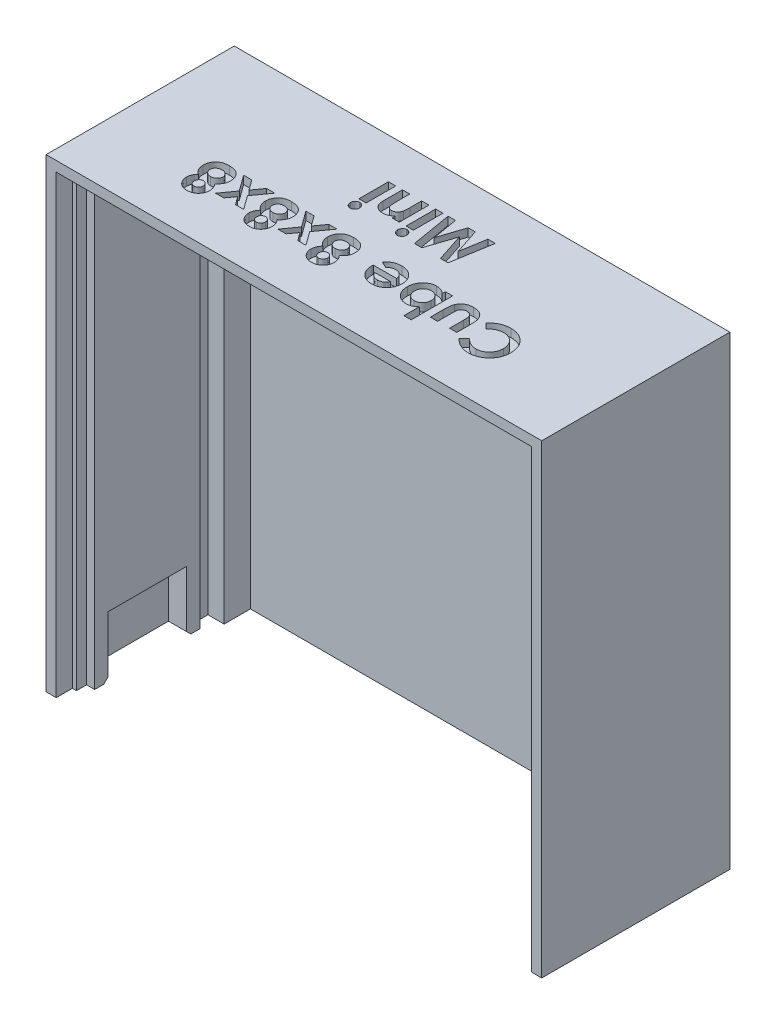
SolidWorks part; units mm, degrees
ref_plane "Plan de face" through (0, 0, 0) normal (0, 0, 1) x (1, 0, 0)
ref_plane "Plan de dessus" through (0, 0, 0) normal (0, 1, 0) x (1, 0, 0)
ref_plane "Plan de droite" through (0, 0, 0) normal (1, 0, 0) x (0, 0, -1)
sketch "Esquisse1" plane through (0, 0, 0) normal (0, 0, 1) x (1, 0, 0)
  line L1 (24.5, -23) -> (-24.5, -23)
  line L2 (24.5, -23) -> (24.5, 23)
  line L3 (24.5, 23) -> (-24.5, 23)
  line L4 (-24.5, -23) -> (-24.5, 23)
  line L5 (24.5, -23) -> (-24.5, 23) construction
  line L6 (24.5, 23) -> (-24.5, -23) construction
  point P0 (0, 0)
  dimension "D1" = 46
  dimension "D2" = 49
extrude "Boss.-Extru.1" add sketch "Esquisse1" along normal blind 1.4
sketch "Esquisse2" plane through (0, 0, 1.4) normal (0, 0, 1) x (1, 0, 0)
  line L0 (-24.5, -23) -> (-24.5, 23)
  line L1 (-24.5, 23) -> (24.5, 23)
  line L2 (24.5, 23) -> (24.5, -23)
  line L3 (24.5, -23) -> (21.5, -23)
  line L4 (-24.5, -23) -> (24.5, -23) construction
  line L5 (21.5, -23) -> (21.5, 20)
  line L6 (21.5, 20) -> (-21.5, 20)
  line L7 (-21.5, 20) -> (-21.5, -23)
  line L8 (-21.5, -23) -> (-24.5, -23)
  dimension "D1" = 3
  dimension "D2" = 3
  dimension "D3" = 3
extrude "Boss.-Extru.2" add sketch "Esquisse2" along normal blind 17.2
sketch3d "Esquisse3D1"
  line L0 (-21.5, 20, 18.6) -> (-21.5, 20, 1.4) construction
  line L1 (-21.5, 20, 4) -> (-21.5, 20, 5.6)
  line L2 (-21.5, 20, 4) -> (-21.5, -23, 4)
  line L3 (-21.5, -23, 4) -> (-21.5, -23, 5.6)
  line L4 (-21.5, 20, 5.6) -> (-21.5, -23, 5.6)
  line L5 (-21.5, -23, 18.6) -> (-21.5, -23, 1.4) construction
  line L7 (-21.5, 20, 16) -> (-21.5, 20, 17.6)
  line L8 (-21.5, 20, 16) -> (-21.5, -23, 16)
  line L9 (-21.5, -23, 16) -> (-21.5, -23, 17.6)
  line L10 (-21.5, 20, 17.6) -> (-21.5, -23, 17.6)
  point P8 (-21.5, -23, 1.4)
  dimension "D1" = 1.6
  dimension "D2" = 2.6
  dimension "D3" = 1.6
  dimension "D4" = 10.4
extrude "Enlèv. mat.-Extru.1" cut sketch "Esquisse3D1" along direction (-1, 0, 0) on the side against the normal blind 1.6 contours L8 L7 L10 L9 | L2 L1 L4 L3
sketch "Esquisse6" plane through (21.5, 0, 0) normal (-1, 0, 0) x (0, 0, 1)
  line L0 (18.6, 20) -> (1.4, 20) construction
  line L1 (4, 20) -> (5.6, 20)
  line L2 (4, 20) -> (4, -23)
  line L3 (4, -23) -> (5.6, -23)
  line L4 (5.6, 20) -> (5.6, -23)
  line L5 (18.6, -23) -> (1.4, -23) construction
  line L6 (1.4, 20) -> (1.4, -23) construction
  line L7 (16, -23) -> (17.6, -23)
  line L8 (16, -23) -> (16, 20)
  line L9 (16, 20) -> (17.6, 20)
  line L10 (17.6, -23) -> (17.6, 20)
  dimension "D1" = 1.6
  dimension "D2" = 1.6
  dimension "D3" = 2.6
  dimension "D4" = 10.4
extrude "Enlèv. mat.-Extru.2" cut sketch "Esquisse6" against normal blind 1.6
sketch "Esquisse7" plane through (0, 20, 0) normal (0, -1, 0) x (1, 0, 0)
  line L1 (-23.1, 17.6) -> (23.1, 17.6)
  line L2 (-23.1, 17.6) -> (-23.1, 16)
  line L3 (-23.1, 16) -> (23.1, 16)
  line L4 (23.1, 17.6) -> (23.1, 16)
  line L5 (-23.1, 4) -> (23.1, 4)
  line L6 (-23.1, 4) -> (-23.1, 5.6)
  line L7 (-23.1, 5.6) -> (23.1, 5.6)
  line L8 (23.1, 4) -> (23.1, 5.6)
extrude "Enlèv. mat.-Extru.3" cut sketch "Esquisse7" against normal blind 1.6
sketch "Esquisse8" plane through (0, 0, 18.6) normal (0, 0, 1) x (1, 0, 0)
  line L0 (-21.5, -23) -> (21.5, -23) construction
  line L1 (-24.5, -23) -> (-21.5, -23) construction
  line L2 (-21.5, -23) -> (-21.5, 20)
  line L3 (-21.5, 20) -> (21.5, 20)
  line L4 (21.5, -23) -> (24.5, -23) construction
  line L5 (23.5, -23) -> (23.5, 22)
  line L6 (23.5, 22) -> (-23.5, 22)
  line L7 (-23.5, 22) -> (-23.5, -23)
  line L8 (-23.5, -23) -> (-21.5, -23)
  line L12 (21.5, 20) -> (21.5, -23)
  line L13 (21.5, -23) -> (23.5, -23)
  line L14 (-24.5, 23) -> (-24.5, -23) construction
  line L15 (24.5, -23) -> (24.5, 23) construction
  line L16 (24.5, 23) -> (-24.5, 23) construction
  dimension "D1" = 1
  dimension "D2" = 1
  dimension "D3" = 1
extrude "Enlèv. mat.-Extru.4" cut sketch "Esquisse8" against normal blind 1.6 and the other way through all
sketch "Esquisse9" plane through (0, -23, 0) normal (0, -1, 0) x (1, 0, 0)
  line L0 (-24.5, 18.6) -> (-24.5, 0) construction
  line L1 (-21.9, 14.7) -> (-24.1, 14.7)
  line L2 (-21.9, 14.7) -> (-21.9, 6.9)
  line L3 (-21.9, 6.9) -> (-24.1, 6.9)
  line L4 (-24.1, 14.7) -> (-24.1, 6.9)
  line L5 (-21.9, 14.7) -> (-24.1, 6.9) construction
  line L6 (-21.9, 6.9) -> (-24.1, 14.7) construction
  line L7 (23.1, 5.6) -> (-23.1, 5.6) construction
  point P0 (-23, 10.8)
  dimension "D1" = 2.2
  dimension "D2" = 1.5
  dimension "D3" = 7.8
  dimension "D4" = 5.2
extrude "Enlèv. mat.-Extru.5" cut sketch "Esquisse9" against normal blind 6
chamfer "Chanfrein1" distance 0.4 angle 45 4 edges at (-23, -23, 6.9) (-24.1, -23, 10.8) (-23, -23, 14.7) (-21.9, -23, 10.8)
sketch "Esquisse13" plane through (0, 23, 0) normal (0, 1, 0) x (1, 0, 0)
  line L0 (24.5, -10.6) -> (-24.5, -10.6) construction
  line L1 (24.5, -18.6) -> (-24.5, -18.6) construction
  line L2 (-24.5, -4) -> (24.5, -4) construction
  line L3 (24.5, 0) -> (-24.5, 0) construction
  line L4 (-24.5, -18.6) -> (-24.5, 0) construction
  line L5 (24.5, -18.6) -> (24.5, 0) construction
  text T0 "<b>Cube 8x8x8</b>" font "Century Gothic" height 4
  text T1 "<b>Mini</b>" font "Century Gothic" height 4
  dimension "8" = 8
  dimension "D3" = 4
extrude "Enlèv. mat.-Extru.9" cut sketch "Esquisse13" against normal blind 0.8
sketch "Esquisse14" plane through (0, -23, 0) normal (0, -1, 0) x (1, 0, 0)
  line L1 (-21.5, 16) -> (-22.3, 16)
  line L2 (-21.5, 16) -> (-21.5, 5.6)
  line L3 (-21.5, 5.6) -> (-22.3, 5.6)
  line L4 (-22.3, 16) -> (-22.3, 5.6)
  line L6 (-21.5, 5.6) -> (-23.1, 5.6) construction
  point P5 (0, 0)
  point P7 (0, 0)
  point P8 (0, 0)
  point P9 (0, 0)
  dimension "D1" = 0.8
extrude "Enlèv. mat.-Extru.10" cut sketch "Esquisse14" against normal up to surface (43 mm away) up to face at (-5.375, 20, 3.025)
mirror "Symétrie2" about plane through (0, 0, 0) normal (1, 0, 0) of "Enlèv. mat.-Extru.10", "Enlèv. mat.-Extru.5", "Chanfrein1"
